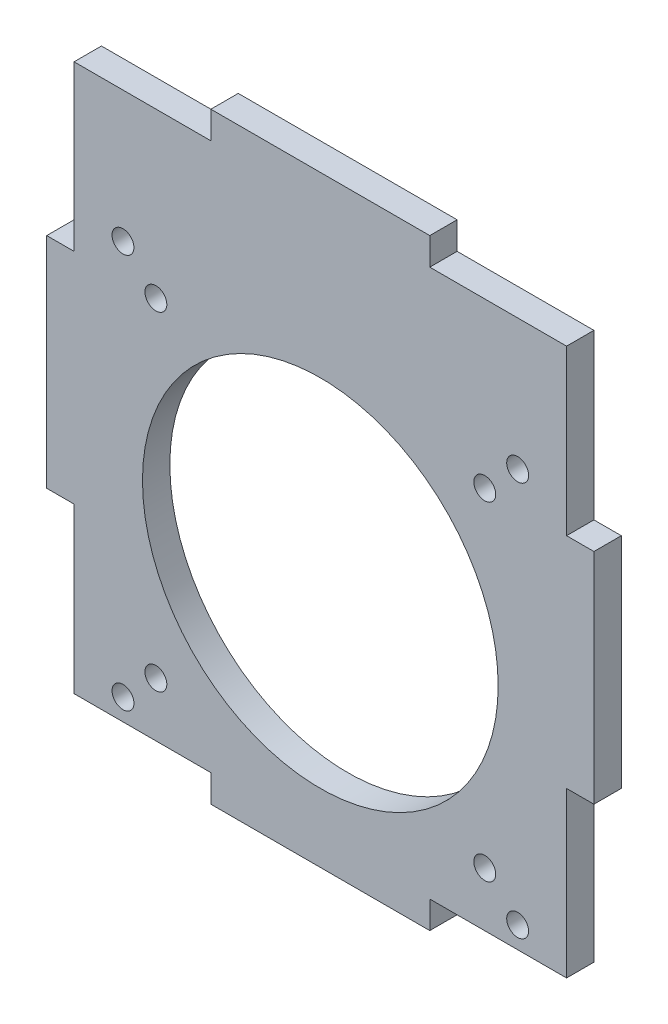
SolidWorks part; units mm, degrees
ref_plane "Front Plane" through (0, 0, 0) normal (0, 0, 1) x (1, 0, 0)
ref_plane "Top Plane" through (0, 0, 0) normal (0, 1, 0) x (1, 0, 0)
ref_plane "Right Plane" through (0, 0, 0) normal (1, 0, 0) x (0, 0, -1)
sketch "Sketch1" plane through (0, 0, 0) normal (0, 0, 1) x (1, 0, 0)
  line L0 (0, 93.0779) -> (0, -81.1469) construction
  line L1 (36.06, -36.06) -> (-36.06, -36.06) construction
  line L2 (36.06, -36.06) -> (36.06, 36.06) construction
  line L3 (36.06, 36.06) -> (-36.06, 36.06) construction
  line L4 (-36.06, -36.06) -> (-36.06, 36.06) construction
  line L5 (36.06, -36.06) -> (-36.06, 36.06) construction
  line L6 (36.06, 36.06) -> (-36.06, -36.06) construction
  line L7 (45, -40) -> (20, -40)
  line L8 (45, -40) -> (45, -10)
  line L9 (45, 60) -> (20, 60)
  line L10 (-45, -40) -> (-45, -10)
  line L11 (45, -40) -> (-45, 60) construction
  line L12 (45, 60) -> (-45, -40) construction
  line L13 (-49.3833, 10) -> (54.7976, 10) construction
  line L14 (-20, 65) -> (-20, 60)
  line L15 (-50, -10) -> (-45, -10)
  line L16 (20, 65) -> (20, 60)
  line L17 (-50, 30) -> (-45, 30)
  line L18 (20, 65) -> (-20, 65)
  line L19 (-50, -10) -> (-50, 30)
  line L20 (20, -45) -> (-20, -45)
  line L21 (50, -10) -> (50, 30)
  line L22 (-49.3833, 30) -> (54.7976, 30) construction
  line L23 (-49.3833, -10) -> (54.7976, -10) construction
  line L25 (-20, 93.0779) -> (-20, -81.1469) construction
  line L26 (50, 65) -> (-50, 65) construction
  line L27 (-50, -45) -> (-50, 65) construction
  line L28 (-45, 30) -> (-45, 60)
  line L29 (-20, 60) -> (-45, 60)
  line L30 (-45, -40) -> (-45, 60) construction
  line L31 (50, -45) -> (-50, -45) construction
  line L32 (20, 93.0779) -> (20, -81.1469) construction
  line L33 (50, -45) -> (50, 65) construction
  line L35 (45, 60) -> (-45, 60) construction
  line L37 (20, -40) -> (20, -45)
  line L38 (-20, -40) -> (-45, -40)
  line L39 (-20, -40) -> (-20, -45)
  line L40 (45, -40) -> (-45, -40) construction
  line L42 (45, 30) -> (45, 60)
  line L43 (45, 30) -> (50, 30)
  line L44 (45, -40) -> (45, 60) construction
  line L45 (45, -10) -> (50, -10)
  circle A0 centre (-36.06, 36.06) radius 2
  circle A1 centre (36.06, 36.06) radius 2
  circle A2 centre (36.06, -36.06) radius 2
  circle A3 centre (-36.06, -36.06) radius 2
  circle A4 centre (0, 0) radius 32.5
  circle A5 centre (-30.052, 30.052) radius 2
  circle A6 centre (30.052, 30.052) radius 2
  circle A7 centre (30.052, -30.052) radius 2
  circle A8 centre (-30.052, -30.052) radius 2
  point P0 (0, 0)
  point P6 (0, 10)
  point P63 (0, 0)
  dimension "D2" = 4
  dimension "D17" = 65
  dimension "D18" = 4
  dimension "D1" = 72.12
  dimension "D3" = 2
  dimension "D5" = 36.06
  dimension "D6" = 36.06
  dimension "D7" = 90
  dimension "D8" = 100
  dimension "D9" = 10
  dimension "D10" = 20
  dimension "D12" = 5
  dimension "D13" = 20
  dimension "D14" = 20
  dimension "D15" = 20
  dimension "D16" = 20
  dimension "D19" = 42.5
  dimension "D21" = 30.052
  dimension "D11" = 20
  dimension "D4" = 2
  dimension "D20" = 4
extrude "Boss-Extrude1" add sketch "Sketch1" along normal blind 5
ref_axis "Axis1" [suppressed] through (36.06, -36.06, 5) along (0, 0, -1)
ref_axis "Axis2" through (-36.06, -36.06, 5) along (0, 0, -1)
